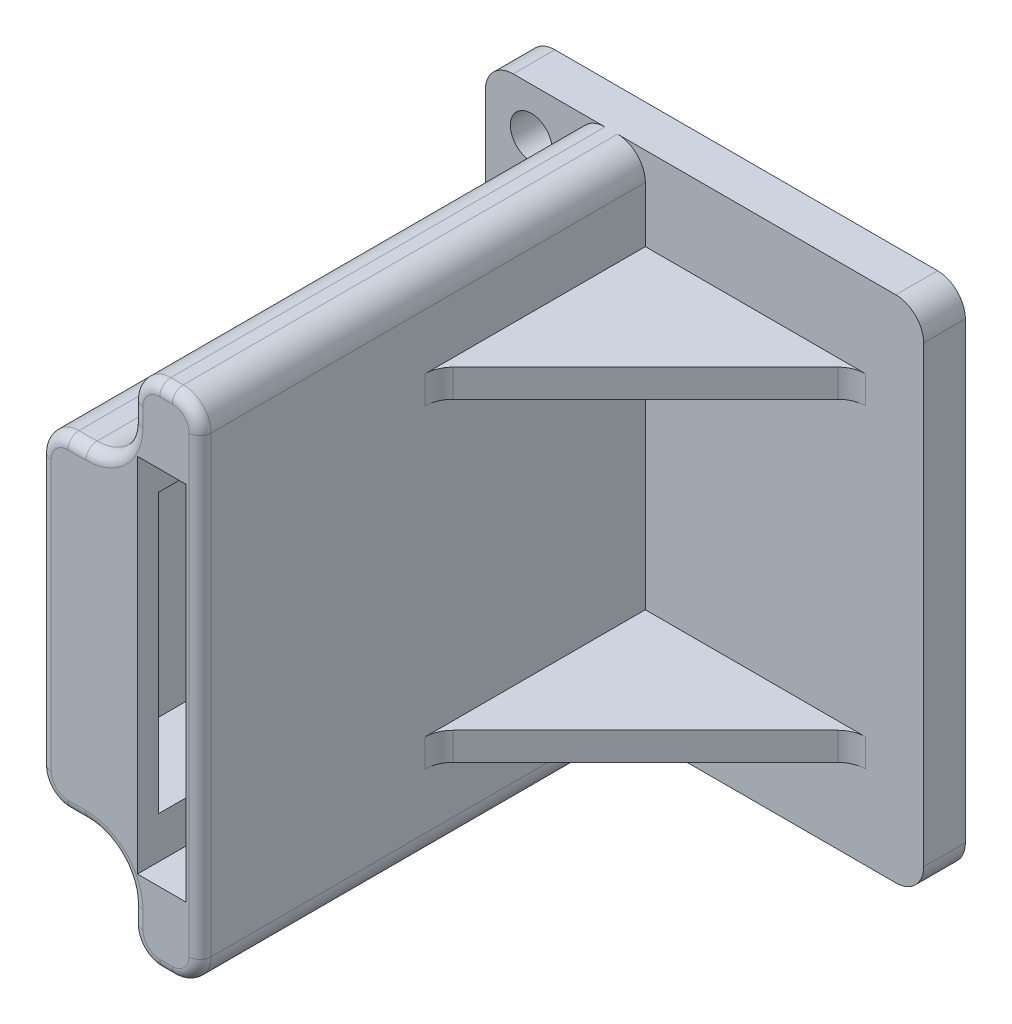
SolidWorks part; units mm, degrees
ref_plane "Front Plane" through (0, 0, 0) normal (0, 0, 1) x (1, 0, 0)
ref_plane "Top Plane" through (0, 0, 0) normal (0, 1, 0) x (1, 0, 0)
ref_plane "Right Plane" through (0, 0, 0) normal (1, 0, 0) x (0, 0, -1)
sketch "Sketch1" plane through (0, 0, 0) normal (0, 0, 1) x (1, 0, 0)
  line L0 (4.191, 46.482) -> (4.191, 42.291) construction
  line L1 (0, 0) -> (14.605, 0)
  line L2 (0, 0) -> (0, 46.482)
  line L3 (0, 46.482) -> (14.605, 46.482)
  line L4 (14.605, 0) -> (14.605, 46.482)
  line L5 (4.191, 0) -> (4.191, 4.191) construction
  circle A0 centre (4.191, 42.291) radius 1.905
  circle A1 centre (4.191, 4.191) radius 1.905
  dimension "D4" = 3.81
  dimension "D1" = 14.605
  dimension "D2" = 4.191
  dimension "D3" = 4.191
  dimension "D5" = 38.1
extrude "Boss-Extrude1" add sketch "Sketch1" along normal blind 44.45
sketch "Sketch2" plane through (0, 0, 44.45) normal (0, 0, 1) x (1, 0, 0)
  line L0 (14.605, 23.241) -> (13.335, 23.241) construction
  line L1 (13.335, 39.751) -> (8.89, 39.751)
  line L2 (13.335, 39.751) -> (13.335, 6.731)
  line L3 (13.335, 6.731) -> (8.89, 6.731)
  line L4 (8.89, 39.751) -> (8.89, 6.731)
  line L5 (14.605, 0) -> (14.605, 46.482) construction
  dimension "D1" = 33.02
  dimension "D2" = 4.445
  dimension "D3" = 1.27
extrude "Cut-Extrude1" cut sketch "Sketch2" against normal blind 38.1
sketch "Sketch3" plane through (13.335, 0, 0) normal (-1, 0, 0) x (0, 0, 1)
  line L0 (0, 46.482) -> (0, 0) construction
  line L1 (0, 35.941) -> (42.545, 35.941)
  line L2 (0, 35.941) -> (0, 10.541)
  line L3 (0, 10.541) -> (42.545, 10.541)
  line L4 (42.545, 35.941) -> (42.545, 10.541)
  line L5 (44.45, 23.241) -> (42.545, 23.241) construction
  line L6 (44.45, 46.482) -> (44.45, 0) construction
  dimension "D1" = 1.905
  dimension "D2" = 25.4
extrude "Cut-Extrude2" cut sketch "Sketch3" along normal offset from surface (12.065 mm away) 1.27 up to face at (0, 23.241, 22.225)
sketch "Sketch4" plane through (0, 0, 44.45) normal (0, 0, 1) x (1, 0, 0)
  line L0 (0, 46.482) -> (0, 0) construction
  line L1 (4.191, 38.1) -> (0, 38.1)
  line L2 (8.382, 42.291) -> (8.382, 46.482)
  line L3 (14.605, 46.482) -> (0, 46.482) construction
  line L4 (4.191, 8.382) -> (0, 8.382)
  line L5 (8.382, 4.191) -> (8.382, 0)
  line L6 (0, 0) -> (14.605, 0) construction
  line L7 (0, 38.1) -> (0, 46.482)
  line L8 (0, 46.482) -> (8.382, 46.482)
  line L9 (0, 8.382) -> (0, 0)
  line L10 (0, 0) -> (8.382, 0)
  arc A0 (4.191, 38.1) -> (8.382, 42.291) centre (4.191, 42.291) ccw
  arc A1 (8.382, 4.191) -> (4.191, 8.382) centre (4.191, 4.191) ccw
extrude "Cut-Extrude3" cut sketch "Sketch4" against normal blind 40.64
sketch "Sketch5" plane through (0, 0, 0) normal (0, 0, -1) x (-1, 0, 0)
  line L0 (0, 0) -> (-14.605, 0) construction
  line L1 (-14.605, 46.482) -> (-40.005, 46.482)
  line L2 (-14.605, 46.482) -> (-14.605, 0)
  line L3 (-14.605, 0) -> (-40.005, 0)
  line L4 (-40.005, 46.482) -> (-40.005, 0)
  line L5 (-14.605, 0) -> (-14.605, 46.482) construction
  line L6 (-14.605, 46.482) -> (0, 46.482) construction
  dimension "D1" = 25.4
extrude "Boss-Extrude2" add sketch "Sketch5" against normal up to surface (3.81 mm away) up to face at (6.096, 42.291, 3.81)
fillet "Fillet1" radius 2.54 10 edges at (8.382, 46.482, 24.13) (0, 38.1, 24.13) (0, 8.382, 24.13) (8.382, 0, 24.13) (0, 0, 1.905) (0, 46.482, 1.905) (40.005, 0, 1.905) (40.005, 46.482, 1.905)
fillet "Fillet2" radius 1.016 16 edges at (0.7439, 37.3561, 44.45) (3.3655, 38.1, 44.45) (7.1545, 39.3275, 44.45) (8.382, 43.1165, 44.45) (9.1259, 45.7381, 44.45) (11.4935, 46.482, 44.45) (13.8611, 45.7381, 44.45) (14.605, 23.241, 44.45) (13.8611, 0.7439, 44.45) (11.4935, 0, 44.45) (9.1259, 0.7439, 44.45) (8.382, 3.3655, 44.45) (7.1545, 7.1545, 44.45) (3.3655, 8.382, 44.45) (0.7439, 9.1259, 44.45) (0, 23.241, 44.45)
chamfer "Chamfer1" distance 7.62 angle 45 1 edges at (1.27, 23.241, 42.545)
sketch "Sketch6" plane through (0, 0, 0) normal (0, -1, 0) x (1, 0, 0)
  line L0 (14.605, 22.86) -> (33.655, 3.81)
  line L1 (14.605, 43.434) -> (14.605, 3.81) construction
  line L2 (37.465, 3.81) -> (12.065, 3.81) construction
  line L3 (33.655, 3.81) -> (14.605, 3.81)
  line L4 (14.605, 3.81) -> (14.605, 22.86)
  dimension "D1" = 19.05
extrude "Boss-Extrude3" add sketch "Sketch6" against normal blind 2.54 from offset 7.62 offset against normal yes
ref_plane "Plane1" through (0, 23.241, 0) normal (0, -1, 0) x (1, 0, 0)
mirror "Mirror1" about plane through (0, 23.241, 0) normal (0, -1, 0) of "Boss-Extrude3"
fillet "Fillet4" radius 2.54 4 edges at (33.655, 8.89, 3.81) (33.655, 37.592, 3.81) (14.605, 37.592, 22.86) (14.605, 8.89, 22.86)
